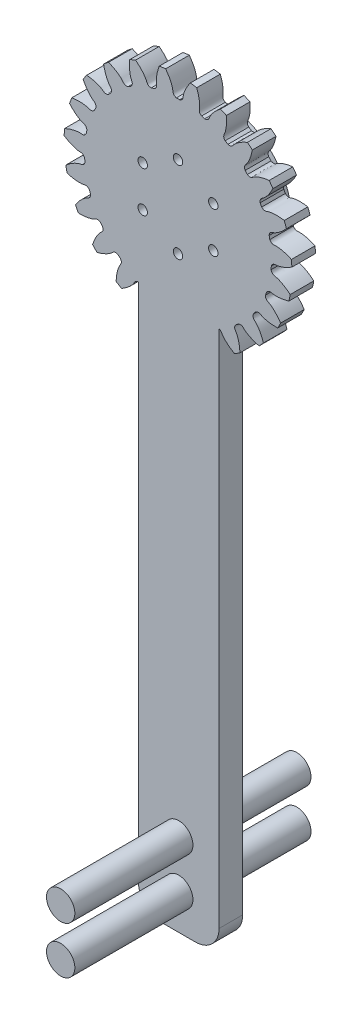
SolidWorks part; units mm, degrees
ref_plane "前视基准面" through (0, 0, 0) normal (0, 0, 1) x (1, 0, 0)
ref_plane "上视基准面" through (0, 0, 0) normal (0, 1, 0) x (1, 0, 0)
ref_plane "右视基准面" through (0, 0, 0) normal (1, 0, 0) x (0, 0, -1)
sketch "草图1" plane through (0, 0, 0) normal (0, 0, 1) x (1, 0, 0)
  circle A0 centre (0, 0) radius 48.25
extrude "凸台-拉伸1" add sketch "草图1" along normal blind 10
ref_axis "基准轴1" through (0, 0, -1.5) along (0, 0, 1)
sketch "草图2" plane through (0, 0, 0) normal (0, 0, 1) x (1, 0, 0)
  line L0 (0, 0) -> (0, 48.25) construction
  circle A0 centre (0, 0) radius 48.25 construction
  arc A1 (0.7001, 39.5588) -> (-0.7001, 39.5588) centre (0, 0) ccw
  arc A2 (12.2813, 54.7587) -> (-12.2813, 54.7587) centre (0, 0) ccw
  spline S0 degree 3 poles (0.7001, 39.5588) (2.2301, 40.0157) (2.0989, 41.0466) (2.2887, 42.0631) (2.3141, 42.1856) (2.3456, 42.3239) (2.3839, 42.4778) (2.4296, 42.6469) (2.4833, 42.8311) (2.5457, 43.0301) (2.6174, 43.2437) (2.6989, 43.4715) (2.791, 43.7132) (2.894, 43.9685) (3.0088, 44.237) (3.1357, 44.5184) (3.2754, 44.8123) (3.4283, 45.1182) (3.5952, 45.4358) (3.7764, 45.7646) (3.9725, 46.1042) (4.1839, 46.4541) (4.4112, 46.8137) (4.6549, 47.1827) (4.9154, 47.5605) (5.1931, 47.9465) (5.4885, 48.3403) (5.802, 48.7412) (6.1339, 49.1487) (6.4848, 49.5622) (6.8549, 49.9811) (7.2445, 50.4049) (7.6542, 50.8328) (8.084, 51.2642) (8.5345, 51.6985) (9.0057, 52.1351) (9.4981, 52.5733) (10.0118, 53.0124) (10.5471, 53.4517) (11.2986, 54.0437) (11.8822, 54.4754) (12.2813, 54.7587) knots 0 0 0 0 0.147387 0.15296 0.159389 0.166677 0.174821 0.183823 0.193683 0.204399 0.215973 0.228404 0.241693 0.255839 0.270842 0.286703 0.303421 0.320996 0.339428 0.358718 0.378866 0.39987 0.421732 0.444451 0.468028 0.492462 0.517753 0.543901 0.570907 0.59877 0.627491 0.657069 0.687504 0.718796 0.750946 0.783953 0.817818 0.85254 0.888119 0.924555 1 1 1 1
  spline S1 degree 3 poles (-0.7001, 39.5588) (-2.2301, 40.0157) (-2.0989, 41.0466) (-2.2887, 42.0631) (-2.3141, 42.1856) (-2.3456, 42.3239) (-2.3839, 42.4778) (-2.4296, 42.6469) (-2.4833, 42.8311) (-2.5457, 43.0301) (-2.6174, 43.2437) (-2.6989, 43.4715) (-2.791, 43.7132) (-2.894, 43.9685) (-3.0088, 44.237) (-3.1357, 44.5184) (-3.2754, 44.8123) (-3.4283, 45.1182) (-3.5952, 45.4358) (-3.7764, 45.7646) (-3.9725, 46.1042) (-4.1839, 46.4541) (-4.4112, 46.8137) (-4.6549, 47.1827) (-4.9154, 47.5605) (-5.1931, 47.9465) (-5.4885, 48.3403) (-5.802, 48.7412) (-6.1339, 49.1487) (-6.4848, 49.5622) (-6.8549, 49.9811) (-7.2445, 50.4049) (-7.6542, 50.8328) (-8.084, 51.2642) (-8.5345, 51.6985) (-9.0057, 52.1351) (-9.4981, 52.5733) (-10.0118, 53.0124) (-10.5471, 53.4517) (-11.2986, 54.0437) (-11.8822, 54.4754) (-12.2813, 54.7587) knots 0 0 0 0 0.147387 0.15296 0.159389 0.166677 0.174821 0.183823 0.193683 0.204399 0.215973 0.228404 0.241693 0.255839 0.270842 0.286703 0.303421 0.320996 0.339428 0.358718 0.378866 0.39987 0.421732 0.444451 0.468028 0.492462 0.517753 0.543901 0.570907 0.59877 0.627491 0.657069 0.687504 0.718796 0.750946 0.783953 0.817818 0.85254 0.888119 0.924555 1 1 1 1
extrude "切除-拉伸1" cut sketch "草图2" along normal through all
pattern_circular "阵列(圆周)1" count 23 every 15.652 about axis through (0, 0, -1.5) along (0, 0, 1) of "切除-拉伸1"
sketch "草图3" plane through (0, 0, 0) normal (0, 0, 1) x (1, 0, 0)
  circle A0 centre (0, 0) radius 44.39 construction
  dimension "Dn" = 88.78
sketch "草图4" plane through (0, 0, 10) normal (0, 0, 1) x (1, 0, 0)
  line L0 (-34.3139, -33.9207) -> (34.3139, -33.9207)
  line L1 (-34.3139, -33.9207) -> (-34.3139, -273.9207)
  line L2 (34.3139, -33.9207) -> (34.3139, -273.9207)
  line L3 (-34.3139, -273.9207) -> (34.3139, -273.9207)
sketch "草图5" plane through (0, 0, 10) normal (0, 0, 1) x (1, 0, 0)
  line L0 (0, 0) -> (48.2116, 0) construction
  line L1 (0, 0) -> (-43.3557, 0) construction
  line L3 (-16.7626, 0) -> (17.3985, 0)
  line L4 (-16.7626, 0) -> (-16.7626, -266)
  line L5 (-16.7626, -266) -> (17.3985, -266)
  line L6 (17.3985, 0) -> (17.3985, -266)
  dimension "D1" = 266
extrude "凸台-拉伸5" add sketch "草图5" against normal blind 10
sketch "草图6" plane through (0, 0, 10) normal (0, 0, 1) x (1, 0, 0)
  circle A0 centre (0, 0) radius 17.25 construction
  circle A1 centre (0, 17.25) radius 2
  circle A2 centre (14.9389, 8.625) radius 2
  circle A3 centre (14.9389, -8.625) radius 2
  circle A4 centre (0, -17.25) radius 2
  circle A5 centre (-14.9389, -8.625) radius 2
  circle A6 centre (-14.9389, 8.625) radius 2
  point P17 (0, 0)
  dimension "D1" = 34.5
  dimension "D2" = 6
extrude "切除-拉伸3" cut sketch "草图6" against normal blind 169
sketch "草图7" plane through (0, 0, 0) normal (0, 0, -1) x (-1, 0, 0)
  circle A0 centre (0, 0) radius 29.5
  dimension "D1" = 59
extrude "凸台-拉伸6" add sketch "草图7" along normal blind 8.85
sketch "草图8" plane through (0, 0, -8.85) normal (0, 0, -1) x (-1, 0, 0)
  circle A0 centre (0, 0) radius 17.25 construction
  circle A1 centre (0, 17.25) radius 2
  circle A2 centre (14.9389, 8.625) radius 2
  circle A3 centre (14.9389, -8.625) radius 2
  circle A4 centre (0, -17.25) radius 2
  circle A5 centre (-14.9389, -8.625) radius 2
  circle A6 centre (-14.9389, 8.625) radius 2
  point P17 (0, 0)
  dimension "D1" = 34.5
  dimension "D2" = 6
extrude "切除-拉伸4" cut sketch "草图8" against normal blind 66
sketch "草图14" plane through (0, 0, 10) normal (0, 0, 1) x (1, 0, 0)
  line L0 (0.3179, -266) -> (0.3179, -251) construction
  line L1 (-16.7626, -266) -> (17.3985, -266) construction
  line L2 (0.3179, -251) -> (0.3179, -231) construction
  circle A0 centre (0.3179, -251) radius 6
  circle A1 centre (0.3179, -231) radius 6
  dimension "D2" = 20
  dimension "D1" = 15
extrude "凸台-拉伸8" add sketch "草图14" along normal mid plane 100
fillet "圆角1" radius 10 1 edges at (17.3985, -266, 5) type face fillet first side face at (17.3985, -151.0329, 5) second side face at (0.3179, -266, 5)
fillet "圆角2" radius 10 1 edges at (-16.7626, -266, 5) type face fillet first side face at (-4.6821, -266, 5) second side face at (-16.7626, -150.9903, 5)
